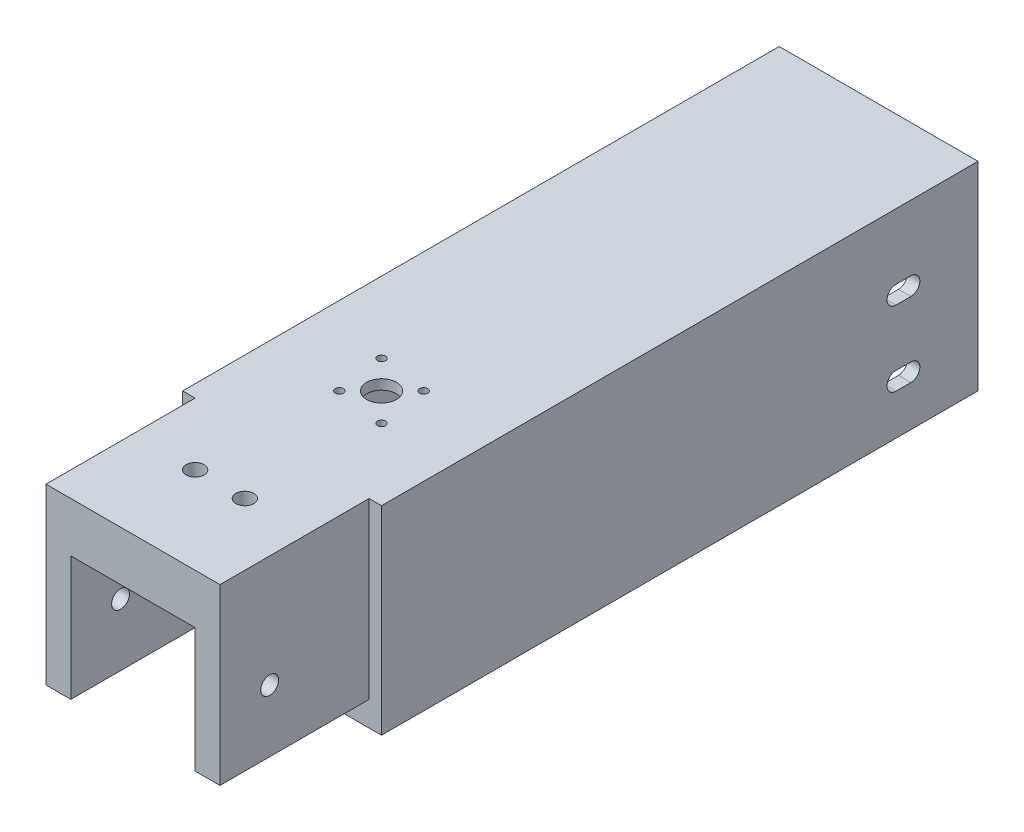
SolidWorks part; units mm, degrees
ref_plane "Front Plane" through (0, 0, 0) normal (0, 0, 1) x (1, 0, 0)
ref_plane "Top Plane" through (0, 0, 0) normal (0, 1, 0) x (1, 0, 0)
ref_plane "Right Plane" through (0, 0, 0) normal (1, 0, 0) x (0, 0, -1)
sketch "Sketch1" plane through (0, 0, 0) normal (0, 1, 0) x (1, 0, 0)
  line L9 (-20, -20) -> (20, -20)
  line L10 (-20, -20) -> (-20, 20)
  line L11 (-20, 20) -> (20, 20)
  line L12 (20, -20) -> (20, 20)
  line L13 (-20, -20) -> (20, 20) construction
  line L14 (-20, 20) -> (20, -20) construction
  circle A0 centre (6.88, 0) radius 2.375
  circle A1 centre (-0.0097, -6.8897) radius 2.375
  circle A2 centre (-6.8993, 0) radius 2.375
  circle A3 centre (-0.0097, 6.8897) radius 2.375
  point P2 (0, 0)
  point P12 (-0.0097, 0)
  dimension "D2" = 4.75
  dimension "D3" = 4
  dimension "D4" = 40
  dimension "D1" = 6.88
  dimension "D5" = 40
extrude "Boss-Extrude1" add sketch "Sketch1" along normal blind 40
sketch "Sketch3" plane through (0, 0, 20) normal (0, 0, 1) x (1, 0, 0)
  line L0 (-20, 0) -> (35335.3391, 35355.3391) construction
  line L1 (-20, 40) -> (35335.3391, -35315.3391) construction
  line L2 (-20, 40) -> (-20, 0) construction
  line L5 (-20, 0) -> (20, 0) construction
  line L6 (20, 40) -> (20, 0) construction
  circle A2 centre (0, 13) radius 3
  circle A3 centre (-7, 20) radius 3
  circle A4 centre (7, 20) radius 3
  point P10 (0, 20)
  dimension "D2" = 6
  dimension "D3" = 6
  dimension "D1" = 6
  dimension "D4" = 13
  dimension "D5" = 13
  dimension "D6" = 13
sketch "Sketch4" plane through (-20, 0, 0) normal (-1, 0, 0) x (0, 0, 1)
  line L0 (-20, 35) -> (-20, 0)
  line L1 (-20, 40) -> (-20, 0) construction
  line L2 (-20, 0) -> (15, 0)
  arc A0 (-20, 35) -> (15, 0) centre (-20, 0) cw
extrude "Cut-Extrude1" cut sketch "Sketch4" along normal through all both and the other way through all
sketch "Sketch6" plane through (0, 0, 0) normal (0, -1, 0) x (1, 0, 0)
  line L0 (20, -20) -> (-20, -20) construction
  line L2 (-15, 15) -> (-15, -20)
  line L3 (-15, -20) -> (15, -20)
  line L4 (15, 15) -> (15, -20)
  line L5 (-11.25, 15) -> (15, -20) construction
  line L6 (-15, -20) -> (11.25, 15) construction
  line L7 (-20, 15) -> (-20, -20) construction
  line L8 (-15, 15) -> (15, 15)
  point P0 (0, 0)
  dimension "D1" = 5
extrude "Cut-Extrude2" cut sketch "Sketch6" against normal blind 35 and the other way through all
extrude "Cut-Extrude3" cut sketch "Sketch3" against normal through all
sketch "Sketch7" plane through (0, 0, 20) normal (0, 0, 1) x (1, 0, 0)
  line L1 (-12.5, 30) -> (12.5, 30) construction
  line L2 (-12.5, 30) -> (-12.5, 5) construction
  line L3 (-12.5, 5) -> (12.5, 5) construction
  line L4 (12.5, 30) -> (12.5, 5) construction
  line L5 (-12.5, 30) -> (12.5, 5) construction
  line L6 (-12.5, 5) -> (12.5, 30) construction
  line L7 (-17.5, 40) -> (17.5, 40)
  line L9 (-12.5, 30) -> (12.5, 30)
  line L12 (-17.5, 23.7908) -> (-17.5, 40)
  line L14 (-12.5, 30) -> (-12.5, 5)
  line L15 (-12.5, 5) -> (-17.5, 5)
  line L16 (-17.5, 23.7908) -> (-17.5, 5)
  line L17 (12.5, 5) -> (17.5, 5)
  line L18 (12.5, 5) -> (12.5, 30)
  line L21 (17.5, 40) -> (17.5, 5)
  line L22 (-20, 40) -> (20, 40) construction
  circle A0 centre (-7, 20) radius 3 construction
  point P0 (0, 17.5)
  dimension "D1" = 7
  dimension "D4" = 10
  dimension "D6" = 5
  dimension "D2" = 25
  dimension "D3" = 25
  dimension "D7" = 5
extrude "Boss-Extrude2" add sketch "Sketch7" along normal blind 30
sketch "Sketch8" plane through (0, 40, 0) normal (0, 1, 0) x (1, 0, 0)
  line L0 (0, -1000) -> (0, 49000) construction
  line L2 (17.5, -20) -> (20, -20) construction
  circle A0 centre (5, -32.5) radius 1.8
  circle A1 centre (-5, -32.5) radius 1.8
  dimension "D3" = 3.6
  dimension "D1" = 5
  dimension "D2" = 12.5
extrude "Cut-Extrude4" cut sketch "Sketch8" against normal through all
sketch "Sketch10" plane through (0, 0, -20) normal (0, 0, -1) x (-1, 0, 0)
  line L2 (-20, 40) -> (-20, 0)
  line L3 (-20, 0) -> (-15, 0)
  line L4 (-15, 35) -> (-15, 0)
  line L5 (15, 0) -> (20, 0)
  line L6 (15, 0) -> (15, 35)
  line L8 (20, 0) -> (20, 40)
  line L9 (15, 35) -> (-15, 35)
  line L10 (20, 35) -> (20, 40)
  line L11 (20, 40) -> (-20, 40)
  line L12 (-20, 35) -> (-20, 40)
  line M5 (-20, 40) -> (-20, 35)
  line M6 (-20, 35) -> (-15, 35)
  line M7 (-15, 35) -> (15, 35)
  line M8 (15, 35) -> (20, 35)
  line M9 (20, 35) -> (20, 40)
  line M10 (20, 40) -> (-20, 40)
  dimension "D1" = 5
sketch "Sketch11" plane through (0, 40, 0) normal (0, 1, 0) x (1, 0, 0)
  circle A0 centre (-0.0097, -6.8897) radius 2.375 construction
  circle A1 centre (6.88, 0) radius 2.375 construction
  circle A2 centre (-0.0097, 6.8897) radius 2.375 construction
  circle A3 centre (-6.8993, 0) radius 2.375 construction
  circle A4 centre (-0.0097, -6.8897) radius 2.375
  circle A5 centre (6.88, 0) radius 2.375
  circle A6 centre (-0.0097, 6.8897) radius 2.375
  circle A7 centre (-6.8993, 0) radius 2.375
extrude "Boss-Extrude4" add sketch "Sketch10" along normal blind 80 and the other way up to surface (40 mm away) contours M10 M5 M6 M7 M8 M9 | L5 L8 L6 M8 | L4 L2 L3 M6 region at (0, 37.5, -20) region at (17.5, 17.5, -20) region at (-17.5, 17.5, -20) other way up to face at (10, 20, 20)
extrude "Cut-Extrude5" cut sketch "Sketch11" against normal blind 70
sketch "Sketch13" plane through (-20, 0, 0) normal (-1, 0, 0) x (0, 0, 1)
  line L0 (-86.5, 25) -> (-83.5, 25) construction
  line L1 (-86.5, 26.8) -> (-83.5, 26.8)
  line L2 (-86.5, 23.2) -> (-83.5, 23.2)
  line L3 (-100, 40) -> (20, 40) construction
  line L4 (-100, 0) -> (-100, 40) construction
  line L5 (-1100, 17.5) -> (48900, 17.5) construction
  line L7 (-100, 0) -> (20, 0) construction
  line L8 (-86.5, 10) -> (-83.5, 10) construction
  line L9 (-86.5, 8.2) -> (-83.5, 8.2)
  line L10 (-86.5, 11.8) -> (-83.5, 11.8)
  arc A0 (-86.5, 26.8) -> (-86.5, 23.2) centre (-86.5, 25) ccw
  arc A1 (-83.5, 23.2) -> (-83.5, 26.8) centre (-83.5, 25) ccw
  arc A2 (-86.5, 8.2) -> (-86.5, 11.8) centre (-86.5, 10) cw
  arc A3 (-83.5, 11.8) -> (-83.5, 8.2) centre (-83.5, 10) cw
  point P2 (-85, 25)
  point P17 (-85, 10)
  dimension "D1" = 1.8
  dimension "D2" = 3
  dimension "D3" = 15
  dimension "D4" = 15
  dimension "D5" = 17.5
extrude "Cut-Extrude6" cut sketch "Sketch13" against normal through all both and the other way through all
sketch "Sketch14" plane through (0, 35, 0) normal (0, -1, 0) x (1, 0, 0)
  line L0 (15, -100) -> (15, 15) construction
  line L1 (-15, -100) -> (15, -100)
  line L2 (-15, -100) -> (-15, -97)
  line L3 (-15, -97) -> (15, -97)
  line L4 (15, -100) -> (15, -97)
  line L5 (-15, 15) -> (-15, -100) construction
  line L6 (-15, -47) -> (15, -47)
  line L7 (-15, -47) -> (-15, -44)
  line L8 (-15, -44) -> (15, -44)
  line L9 (15, -47) -> (15, -44)
  line L10 (-15, -22) -> (-15, -19)
  line L11 (-15, -22) -> (15, -22)
  line L12 (15, -22) -> (15, -19)
  line L13 (-15, -19) -> (15, -19)
  line L14 (-15, 15) -> (-15, -100) construction
  line L15 (-15, -67) -> (15, -67)
  line L16 (-15, -67) -> (-15, -70)
  line L17 (-15, -70) -> (15, -70)
  line L18 (15, -67) -> (15, -70)
  dimension "D1" = 3
  dimension "D2" = 3
  dimension "D3" = 50
  dimension "D4" = 30
  dimension "D6" = 3
  dimension "D7" = 20
  dimension "D5" = 2
extrude "Boss-Extrude10" add sketch "Sketch14" along normal up to surface (35 mm away) up to face at (0, 0, -41.25)
sketch "Sketch16" plane through (0, 35, 0) normal (0, -1, 0) x (1, 0, 0)
  line L1 (15, 15) -> (-15, 15)
  line L2 (15, 15) -> (15, -19)
  line L3 (15, -19) -> (-15, -19)
  line L4 (-15, 15) -> (-15, -19)
extrude "Cut-Extrude7" cut sketch "Sketch16" against normal blind 1.5 and the other way through all
sketch "Sketch17" plane through (0, 0, -47) normal (0, 0, -1) x (-1, 0, 0)
  line L0 (0, -8.5238) -> (0, 5.4762) construction
  line L1 (-15, -8.5238) -> (-15, 5.4762)
  line L2 (15, -8.5238) -> (15, 5.4762)
  line L3 (-15, 0) -> (-15, 35) construction
  arc A0 (-15, -8.5238) -> (15, -8.5238) centre (0, -8.5238) ccw
  arc A1 (15, 5.4762) -> (-15, 5.4762) centre (0, 5.4762) ccw
  point P2 (0, -1.5238)
  dimension "D1" = 7
extrude "Cut-Extrude8" cut sketch "Sketch17" against normal blind 32.5 and the other way blind 32
sketch "Sketch19" plane through (-17.5, 0, 0) normal (-1, 0, 0) x (0, 0, 1)
  line L0 (50, 5) -> (20, 5) construction
  line L1 (50, 40) -> (50, 5) construction
  circle A0 centre (40, 17.5) radius 1.8
  dimension "D1" = 3.6
  dimension "D3" = 10
  dimension "D2" = 12.5
extrude "Cut-Extrude9" cut sketch "Sketch19" against normal through all both and the other way through all
extrude "Boss-Extrude11" add sketch "Sketch3<2>" against normal up to surface (5 mm away) up to face at (-3, 13, 15)
sketch "Sketch3<2>" plane through (0, 0, 20) normal (0, 0, 1) x (1, 0, 0) same geometry as "Sketch3"
sketch "Sketch20" plane through (0, 0, -97) normal (0, 0, 1) x (1, 0, 0)
  line L1 (-15, 35) -> (15, 35)
  line L2 (-15, 35) -> (-15, 0)
  line L3 (-15, 0) -> (15, 0)
  line L4 (15, 35) -> (15, 0)
extrude "Cut-Extrude10" cut sketch "Sketch20" against normal blind 10
sketch "Sketch21" plane through (0, 40, 0) normal (0, 1, 0) x (1, 0, 0)
  circle A0 centre (-0.0097, -6.8897) radius 2.375 construction
  circle A1 centre (6.88, 0) radius 2.375 construction
  circle A2 centre (-0.0097, 6.8897) radius 2.375 construction
  circle A3 centre (-6.8993, 0) radius 2.375 construction
  circle A4 centre (-0.0097, -6.8897) radius 2.375
  circle A5 centre (6.88, 0) radius 2.375
  circle A6 centre (-0.0097, 6.8897) radius 2.375
  circle A7 centre (-6.8993, 0) radius 2.375
sketch "Sketch22" plane through (0, 40, 0) normal (0, 1, 0) x (1, 0, 0)
  circle A0 centre (0, 0) radius 3
  dimension "D1" = 6
extrude "Cut-Extrude11" cut sketch "Sketch22" against normal through all both and the other way through all
extrude "Boss-Extrude13" add sketch "Sketch21" against normal up to surface (3.5 mm away) up to face at (0, 36.5, 3)
sketch "Sketch23" plane through (0, 40, 0) normal (0, 1, 0) x (1, 0, 0)
  line L0 (-4.2426, -4.2426) -> (4.2426, 4.2426) construction
  line L1 (-5.6569, 5.6569) -> (5.6569, -5.6569) construction
  line L2 (-1000, 0) -> (49000, 0) construction
  circle A0 centre (-5.6569, 5.6569) radius 0.815
  circle A1 centre (4.2426, 4.2426) radius 0.815
  circle A2 centre (5.6569, -5.6569) radius 0.815
  circle A3 centre (-4.2426, -4.2426) radius 0.815
  point P5 (0, 0)
  point P8 (0, 0)
  dimension "D5" = 1.63
  dimension "D6" = 1.63
  dimension "D7" = 1.63
  dimension "D8" = 1.63
  dimension "D1" = 45
  dimension "D2" = 45
  dimension "D3" = 16
  dimension "D4" = 12
extrude "Cut-Extrude12" cut sketch "Sketch23" against normal through all both and the other way through all
sketch "Sketch24" plane through (0, 36.5, 0) normal (0, -1, 0) x (1, 0, 0)
  circle A0 centre (0, 0) radius 12.5
  dimension "D1" = 25
extrude "Cut-Extrude13" cut sketch "Sketch24" against normal blind 1.5 and the other way through all
sketch "Sketch25" plane through (0, 0, 0) normal (1, 0, 0) x (0, 0, -1)
  line L0 (83.5, 25) -> (86.5, 25) construction
  line L1 (85, -975) -> (85, 49025) construction
  line L3 (85, 25) -> (85, -7.9224) construction
  line L4 (92.5, 25) -> (92.5, -7.9224)
  line L5 (77.5, 25) -> (77.5, -7.9224)
  arc A0 (92.5, 25) -> (77.5, 25) centre (85, 25) ccw
  arc A1 (77.5, -7.9224) -> (92.5, -7.9224) centre (85, -7.9224) ccw
  point P5 (85, 3.398)
  point P7 (85, 25)
  point P8 (85, -7.9224)
  point P12 (85, 8.5388)
  point P17 (0, 0)
  dimension "D1" = 15
extrude "Cut-Extrude14" cut sketch "Sketch25" against normal blind 17.5 and the other way blind 17.5
